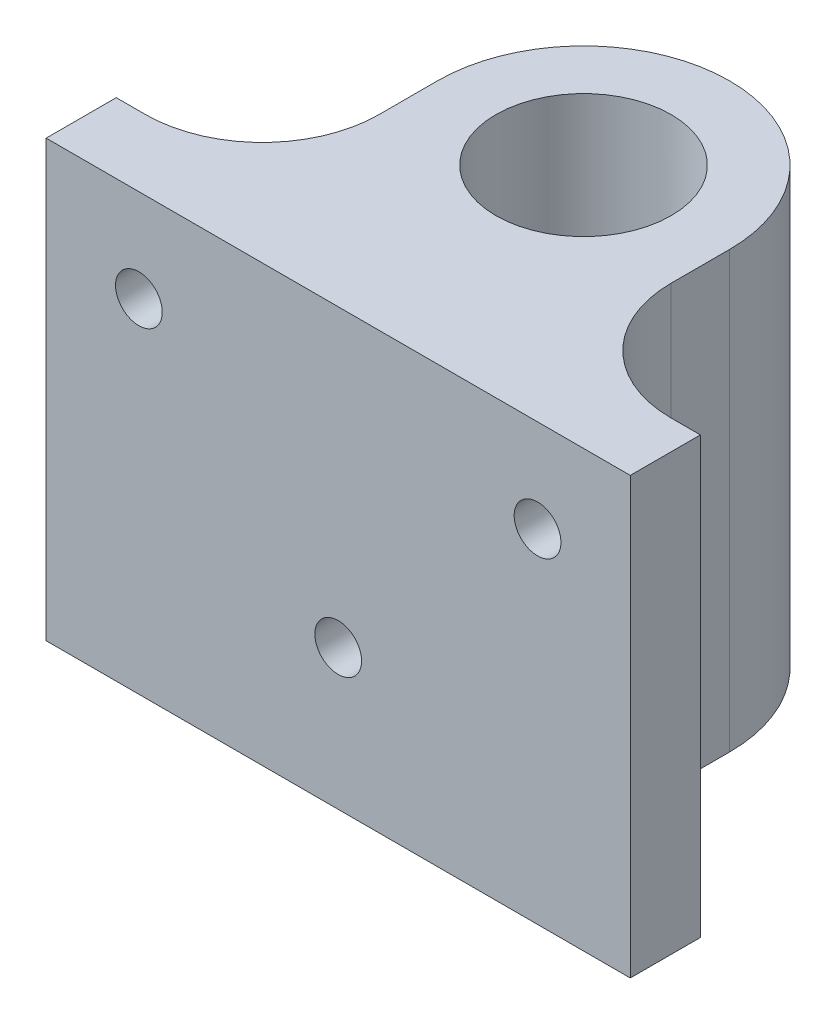
SolidWorks part; units mm, degrees
ref_plane "Front Plane" through (0, 0, 0) normal (0, 0, 1) x (1, 0, 0)
ref_plane "Top Plane" through (0, 0, 0) normal (0, 1, 0) x (1, 0, 0)
ref_plane "Right Plane" through (0, 0, 0) normal (1, 0, 0) x (0, 0, -1)
sketch "Profile-Sketch1" plane through (0, 0, 0) normal (0, 1, 0) x (1, 0, 0)
  line L0 (-25, -21) -> (25, -21)
  line L1 (25, -21) -> (25, -15)
  line L2 (-25, -21) -> (-25, -15)
  line L3 (-25, -15) -> (-22.5, -15)
  line L4 (-12.5, -5) -> (-12.5, 0)
  line L5 (25, -15) -> (22.5, -15)
  line L6 (12.5, -5) -> (12.5, 0)
  circle A0 centre (0, 0) radius 7.5
  arc A6 (12.5, 0) -> (-12.5, 0) centre (0, 0) ccw
  arc A7 (22.5, -15) -> (12.5, -5) centre (22.5, -5) cw
  arc A8 (-12.5, -5) -> (-22.5, -15) centre (-22.5, -5) cw
  dimension "D1" = 15
  dimension "D2" = 12.5
  dimension "D7" = 10
  dimension "D3" = 50
  dimension "D4" = 25
  dimension "D5" = 21
  dimension "D6" = 6
extrude "Profile-Boss-Extrude2" add sketch "Profile-Sketch1" along normal blind 37.2599
sketch "FasteningHoleSketch3" plane through (0, 0, 21) normal (0, 0, 1) x (1, 0, 0)
  line L0 (25, 37.2599) -> (25, 0) construction
  line L1 (-25, 37.2599) -> (-25, 0) construction
  line L2 (-25, 0) -> (25, 0) construction
  circle A2 centre (-17.0625, 29.3224) radius 2
  circle A3 centre (17.0625, 29.3224) radius 2
  dimension "D3" = 4
  dimension "D6" = 7.9375
  dimension "D2" = 29.3224
  dimension "D1" = 7.9375
extrude "FasteningHoleCut-Extrude8" cut sketch "FasteningHoleSketch3" against normal through all
sketch "LM8UUFasteningHoleSketch5" plane through (0, 0, 21) normal (0, 0, 1) x (1, 0, 0)
  line L0 (25, 37.2599) -> (25, 0) construction
  line L1 (-25, 0) -> (25, 0) construction
  line L2 (-25, 37.2599) -> (25, 37.2599) construction
  circle A0 centre (0, 12) radius 2
  circle A1 centre (-17.0625, 29.3224) radius 2 construction
  dimension "D1" = 25
  dimension "D2" = 12
  dimension "D3" = 25.2599
extrude "LM8UUFasteningHoleCut-Extrude9" cut sketch "LM8UUFasteningHoleSketch5" against normal through all
equation "\"RailThickness\"= .125in'Spec"
equation "\"LM8UUDiameter\"= 15mm"
equation "\"MidLeftOrRightSideRailHeight\"= 2.0in"
equation "\"RodStabilizerLength\"= 50mm"
equation "\"HoleOffsetFromEdge\"= \"RailThickness\" * 2.5"
equation "\"StepperMountingHoleOffsetFromItsSide\"= 5.5mm'Spec"
equation "\"StepperMountingHoleOffsetFromLeftOrRightSide\"= \"StepperMountingHoleOffsetFromItsSide\" + \"RailThickness\""
equation "\"StepperMountingHoleDistance\"= 31mm'Spec"
equation "\"LM8UUHeight\"= 24mm'Spec"
equation "\"ZAxisLeadScrewLength\"= 200mm"
equation "\"LegHeight\"= 70mm'Space needed for PSU/Stepper/Electronics"
equation "\"V1 BottomOfLowerRail\"= \"LegHeight\""
equation "\"StepperShaftLength\"= 24mm'Pulley will be attached to the end"
equation "\"V2 ToBedAtTopOfZAxis\"= \"V1 BottomOfLowerRail\" - \"LowerEnclosureThickness\" + \"StepperShaftLength\" + \"ZAxisLeadScrewLength\" - \"LM8UUHeight\" / 2'Equals 277"
equation "\"HotEndToTopOfXAxisGB\"= 71.68487mm'Equals 71.68487. Measured after installed onto X-Axis linear rail guide block"
equation "\"TopOfGBToBottomOfLinearRail\"= \"LinearGBWidth\" / 2 + \"LinearRailWidth\" / 2'Equals 19.5"
equation "\"LinearGBWidth\"= 27mm'Spec"
equation "\"V5 ToBottomOfXAxisLinearRail\"= \"V4 ToTopOfBuildPlate/HotEndTip\" + \"HotEndToTopOfXAxisGB\" - \"TopOfGBToBottomOfLinearRail\"'Equals 352.18487"
equation "\"LinearRailWidth\"= 12mm'Spec"
equation "\"V6 ToMiddleOfYAxisGantryBlock\"= \"V5 ToBottomOfXAxisLinearRail\" - \"GABHeight\" / 2'Equals 334.18487"
equation "\"GABUpperHeight\"= 4mm"
equation "\"GABMidWallHeight\"= 28mm'Must equal 28 or changes alignment"
equation "\"BedToBuildPlateStandoffLength\"= 15mm"
equation "\"BuildPlateHeight\"= 8mm'Spec"
equation "\"V4 ToTopOfBuildPlate/HotEndTip\"= \"V2 ToBedAtTopOfZAxis\" + \"BedToBuildPlateStandoffLength\" + \"BuildPlateHeight\""
equation "\"RodStabilizerHeight\"= \"V8 ToBottomOfMidSideRail\" - \"V2 ToBedAtTopOfZAxis\" + \"HoleOffsetFromEdge\" * 2"
equation "\"LowerEnclosureThickness\"= 5mm"
equation "\"D1@Profile-Sketch1\" = \"LM8UUDiameter\""
equation "\"D3@Profile-Sketch1\" = \"RodStabilizerLength\""
equation "\"D4@Profile-Sketch1\" = \"RodStabilizerLength\" / 2"
equation "\"RodStabilizerWidthFromMidRailToZAxisRodCenter\"= \"StepperMountingHoleOffsetFromLeftOrRightSide\" + \"StepperMountingHoleDistance\" / 2 - \"RailThickness\""
equation "\"StandardWallThickness\"= 3mm"
equation "\"D6@Profile-Sketch1\" = \"StandardWallThickness\" * 2"
equation "\"D1@Profile-Boss-Extrude2\"= \"RodStabilizerHeight\""
equation "\"D6@FasteningHoleSketch3\"=\"HoleOffsetFromEdge\""
equation "\"D2@LM8UUFasteningHoleSketch5\"=\"LM8UUHeight\"/2"
equation "\"V8 ToTopOfMidSideRail\"= \"V6 ToMiddleOfYAxisGantryBlock\" + \"MidSideRailVerticalOffset\"'Equals 349.18487"
equation "\"D5@Profile-Sketch1\"=\"RodStabilizerWidthFromMidRailToZAxisRodCenter\""
equation "\"RodStabilizerMountingHoleYOffsetFromBottom\"= \"RodStabilizerHeight\" - \"HoleOffsetFromEdge\""
equation "\"D2@FasteningHoleSketch3\"=\"RodStabilizerMountingHoleYOffsetFromBottom\""
equation "\"D3@FasteningHoleSketch3\"=\"M3HeatInsertHoleDiameter\""
equation "\"GABLowerHeight\"= 4mm"
equation "\"GABHeight\"= \"GABLowerHeight\" + \"GABMidWallHeight\" + \"GABUpperHeight\""
equation "\"V8 ToBottomOfMidSideRail\"= \"V8 ToTopOfMidSideRail\" - \"MidLeftOrRightSideRailHeight\"'Equals 298.38487"
equation "\"D1@LM8UUFasteningHoleSketch5\"=\"RodStabilizerLength\"/2"
equation "\"MidSideRailVerticalOffset\"= \"LinearRailWidth\" + 3mm'Allows space for RodStabilizer to attach to bottom of MidSideRail"
equation "\"M3HeatInsertHoleDiameter\"= 4mm'Spec"
